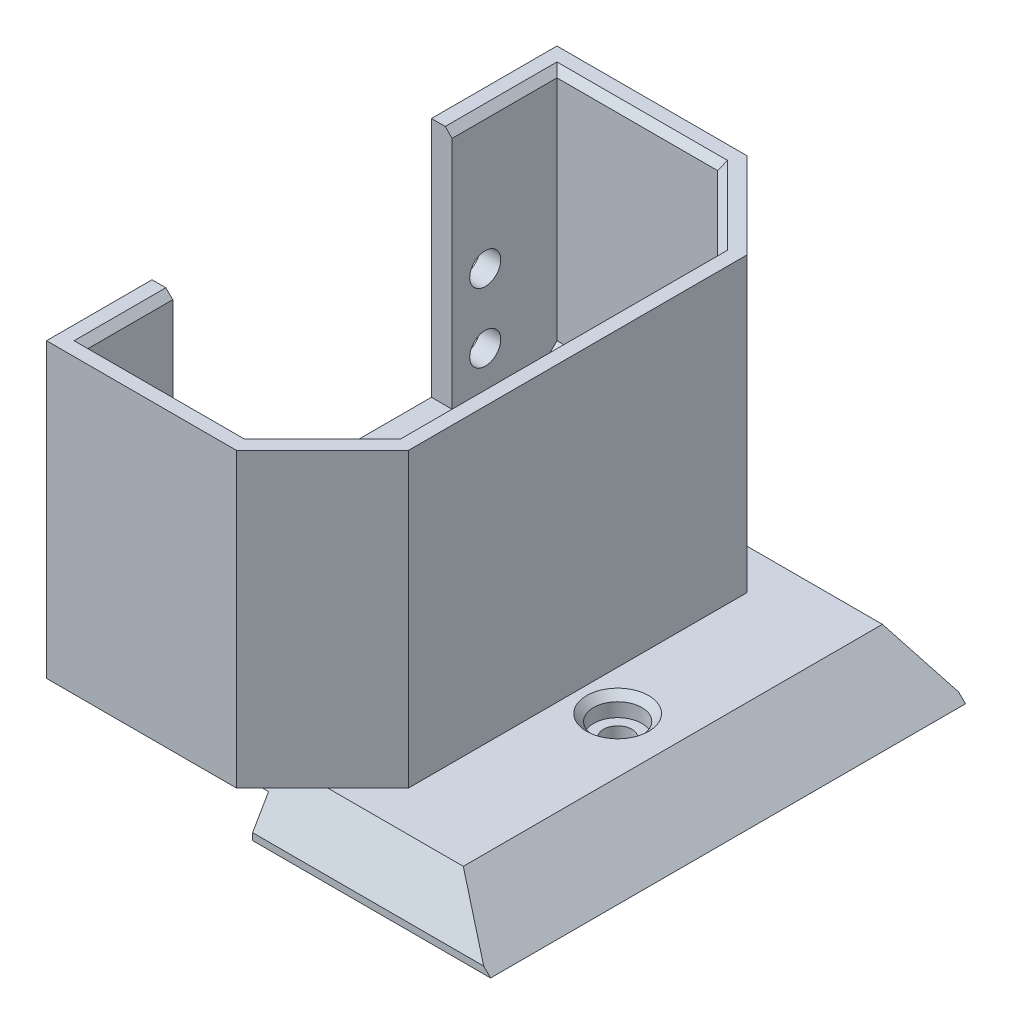
SolidWorks part; units mm, degrees
ref_plane "Front Plane" through (0, 0, 0) normal (0, 0, 1) x (1, 0, 0)
ref_plane "Top Plane" through (0, 0, 0) normal (0, 1, 0) x (1, 0, 0)
ref_plane "Right Plane" through (0, 0, 0) normal (1, 0, 0) x (0, 0, -1)
sketch "Sketch1" plane through (0, 0, 0) normal (0, 1, 0) x (1, 0, 0)
  line L1 (-20, 35) -> (7.5426, 35)
  line L2 (-20, 35) -> (-20, -39)
  line L3 (-20, -39) -> (7.5426, -39)
  line L4 (20, 22.5426) -> (20, -26.5426)
  line L8 (7.5426, 35) -> (20, 22.5426)
  line L9 (7.5426, -39) -> (20, -26.5426)
  line L10 (20, 18.3) -> (3.3, 35) construction
  point P1 (0, 0)
  point P5 (0, 0)
  point P7 (0, 0)
  dimension "D4" = 20
  dimension "D5" = 3
  dimension "D3" = 16.7
  dimension "D2" = 35
  dimension "D6" = 74
  dimension "D1" = 40
extrude "Main Face Extrude" add sketch "Sketch1" along normal blind 7.4
sketch "Sketch3" plane through (0, 7.4, 0) normal (0, 1, 0) x (1, 0, 0)
  line L4 (-20, 35) -> (-20, -39)
  line L5 (-20, -39) -> (7.5426, -39)
  line L6 (20, -26.5426) -> (20, 22.5426)
  line L7 (7.5426, 35) -> (-20, 35)
  line L8 (-20, 35) -> (-20, -39)
  line L9 (-20, -39) -> (7.5426, -39)
  line L10 (20, -26.5426) -> (20, 22.5426)
  line L11 (7.5426, 35) -> (-20, 35)
  line L12 (-17, 32) -> (-17, -36)
  line L13 (-17, -36) -> (6.3, -36)
  line L14 (6.3, -36) -> (17, -25.3)
  line L15 (17, -25.3) -> (17, 21.3)
  line L16 (17, 21.3) -> (6.3, 32)
  line L17 (6.3, 32) -> (-17, 32)
  line L18 (7.5426, -39) -> (20, -26.5426)
  line L19 (7.5426, -39) -> (20, -26.5426)
  line L20 (20, 22.5426) -> (7.5426, 35)
  line L21 (20, 22.5426) -> (7.5426, 35)
  dimension "D1" = 0
  dimension "D2" = 3
extrude "Main Walls Extrude" add sketch "Sketch3" along normal blind 35
chamfer "Main Walls Lower Chamfer" distance 1 angle 45 5 edges at (-5.35, 7.4, 36) (11.65, 7.4, 30.65) (17, 7.4, 2) (11.65, 7.4, -26.65) (-5.35, 7.4, -32)
chamfer "Main Walls Entry Chamfer" distance 1 angle 45 6 edges at (-5.35, 42.4, 36) (11.65, 42.4, 30.65) (17, 42.4, 2) (11.65, 42.4, -26.65) (-17, 42.4, 2) (-5.35, 42.4, -32)
sketch "Sketch4" plane through (0, 42.4, 0) normal (0, 1, 0) x (1, 0, 0)
  line L0 (-17, 32) -> (-17, -36) construction
  line L1 (-17, 16.8) -> (-20, 16.8)
  line L2 (-17, 16.8) -> (-17, -23.7)
  line L3 (-17, -23.7) -> (-20, -23.7)
  line L4 (-20, 16.8) -> (-20, -23.7)
  line L5 (-20, 35) -> (-20, -39) construction
  point P8 (-17, -3.45)
  dimension "D1" = 40.5
  dimension "D2" = 3.45
extrude "Servo Mount Cut" cut sketch "Sketch4" against normal up to surface (35 mm away) up to face at (1.6286, 7.4, 2)
sketch "Sketch5" plane through (-20, 0, 0) normal (-1, 0, 0) x (0, 0, 1)
  line L2 (-21.6, 22.65) -> (-16.8, 22.65) construction
  line L3 (-16.8, 7.4) -> (-16.8, 42.4) construction
  line L4 (28.5, 22.65) -> (23.7, 22.65) construction
  line L5 (23.7, 7.4) -> (23.7, 42.4) construction
  line L6 (25.3, 7.4) -> (-21.3, 7.4) construction
  circle A0 centre (-21.6, 22.65) radius 2.25
  circle A1 centre (-21.6, 12.65) radius 2.25
  circle A2 centre (28.5, 22.65) radius 2.25
  circle A3 centre (28.5, 12.65) radius 2.25
  dimension "D1" = 4.5
  dimension "D2" = 10
  dimension "D3" = 50.1
  dimension "D4" = 5.25
extrude "Servo Mount Holes" cut sketch "Sketch5" against normal up to next
sketch "Sketch8" plane through (-20, 0, 0) normal (-1, 0, 0) x (0, 0, 1)
  line L0 (-28.3812, 0) -> (-32.4226, -7)
  line L1 (-35, 0) -> (39, 0) construction
  line L3 (-32.4226, -8) -> (36.4226, -8)
  line L5 (36.4226, -7) -> (32.3812, 0)
  line L6 (32.3812, 0) -> (-28.3812, 0)
  line L7 (2, -8) -> (2, 0) construction
  line L8 (-32.4226, -8) -> (-32.4226, -7)
  line L9 (36.4226, -8) -> (36.4226, -7)
  line L11 (-33, -8) -> (-32.4226, -8) construction
  line L12 (-32.4226, -7) -> (-33, -8) construction
  line L13 (36.4226, -8) -> (37, -8) construction
  line L14 (37, -8) -> (36.4226, -7) construction
  point P12 (2, 0)
  point P13 (-32.2414, -9)
  dimension "D1" = 60
  dimension "D2" = 8
  dimension "D3" = 1
  dimension "D4" = 70
extrude "Mount Dovetail" add sketch "Sketch8" against normal blind 61.8
chamfer "Mount Dovetail Chamfer" distance 8 angle 45 1 edges at (41.8, 0, 2)
sketch "Sketch9" plane through (0, -8, 0) normal (0, -1, 0) x (1, 0, 0)
  line L0 (41.8, -32.4226) -> (-20, -32.4226) construction
  line L1 (-20, 36.4226) -> (7.3, 36.4226)
  line L2 (-20, 36.4226) -> (-20, -32.4226)
  line L3 (-20, -32.4226) -> (7.3, -32.4226)
  line L4 (7.3, 36.4226) -> (7.3, -32.4226)
  dimension "D1" = 27.3
extrude "Dovetail Offset Cut" cut sketch "Sketch9" against normal blind 5
sketch "Sketch10" plane through (0, 0, 0) normal (0, 1, 0) x (1, 0, 0)
  line L0 (41.8, 32.4226) -> (41.8, -36.4226) construction
  line L1 (41.8, -2) -> (25.8, -2) construction
  circle A0 centre (25.8, -2) radius 2.05
  dimension "D2" = 4.1
  dimension "D1" = 16
extrude "Mount Screw Hole" cut sketch "Sketch10" against normal through all
sketch "Sketch11" plane through (0, 0, 0) normal (0, 1, 0) x (1, 0, 0)
  circle A0 centre (25.8, -2) radius 3.5
  dimension "D1" = 7
extrude "Mount Screw Countersink" cut sketch "Sketch11" against normal blind 3
chamfer "Mount Screw Countersink Chamfer" distance 1 angle 45 1 edges at (25.8, 0, 5.5)
sketch "Sketch2" plane through (0, 7.4, 0) normal (0, 1, 0) x (1, 0, 0)
  line L0 (-20, 35) -> (-20, 16.8) construction
  line L1 (-1.7, 26.5) -> (5.3, 26.5)
  line L2 (-3.7, 24.5) -> (-3.7, -11.5)
  line L3 (-1.7, -13.5) -> (5.3, -13.5)
  line L4 (7.3, 24.5) -> (7.3, -11.5)
  line L6 (-3.7, 24.5) -> (-1.7, 26.5)
  line L7 (-3.7, -11.5) -> (-1.7, -13.5)
  line L8 (5.3, -13.5) -> (7.3, -11.5)
  line L9 (5.3, 26.5) -> (7.3, 24.5)
  line L11 (1.8, 26.5) -> (1.8, -13.5) construction
  line L13 (-3.7, 6.5) -> (7.3, 6.5) construction
  line L15 (-20, -23.7) -> (-20, 16.8) construction
  point P0 (11.8199, 6.5)
  point P3 (-20, -3.45)
  point P4 (1.8, 26.5)
  dimension "D1" = 11
  dimension "D2" = 40
  dimension "D3" = 21.8
  dimension "D4" = 9.95
  dimension "D5" = 2
  dimension "D6" = 2
extrude "Gear Cut" cut sketch "Sketch2" against normal through all
chamfer "Gear Entry Chamfer" distance 3 angle 45 8 edges at (6.3, 7.4, 12.5) (1.8, 7.4, 13.5) (-2.7, 7.4, 12.5) (-3.7, 7.4, -6.5) (-2.7, 7.4, -25.5) (7.3, 7.4, -6.5) (6.3, 7.4, -25.5) (1.8, 7.4, -26.5)
ref_plane "Gear Plane" through (1.8, 0, 0) normal (-1, 0, 0) x (0, 0, 1)
sketch "Reference Gear Shape" plane through (1.8, 0, 0) normal (-1, 0, 0) x (0, 0, 1)
  line L0 (-1006.3434, -4.35) -> (48993.6566, -4.35) construction
  circle A0 centre (-6.5, 17.65) radius 23
  circle A1 centre (-21.6, 22.65) radius 2.25 construction
  dimension "D1" = 46
  dimension "D2" = 15.1
  dimension "D3" = 5
  dimension "D4" = 22
equation "\"D4@Sketch1\"=\"D1@Sketch1\"/2"
